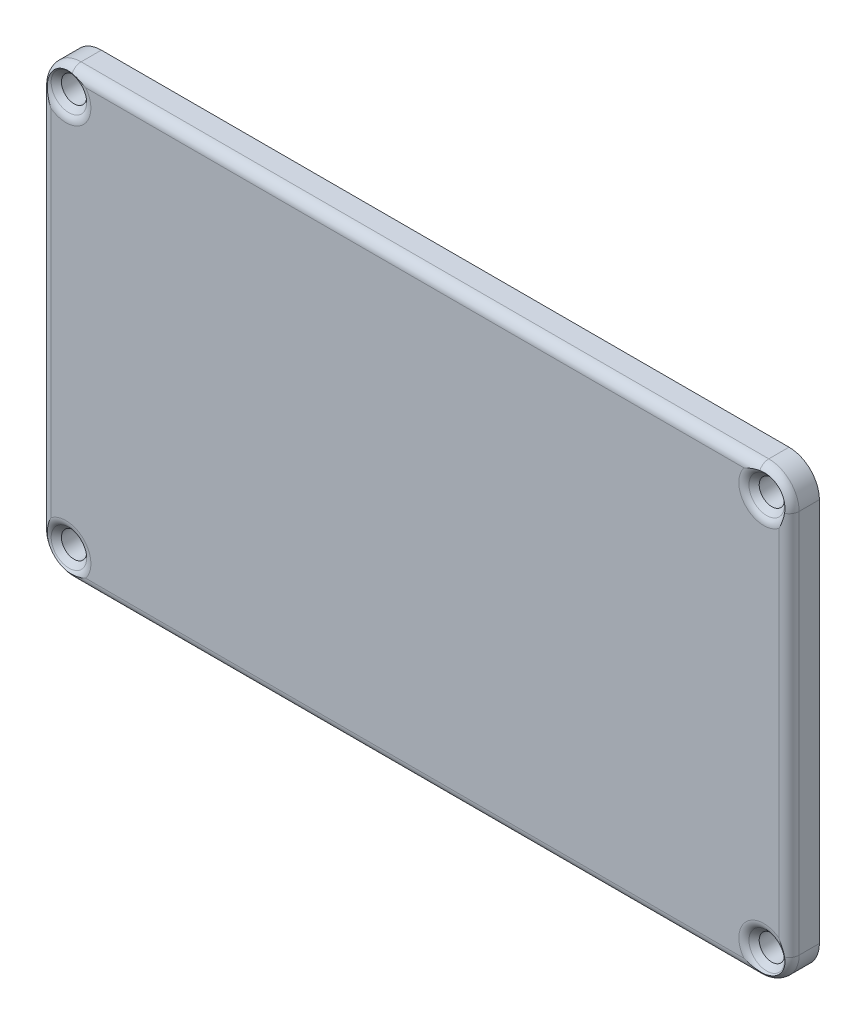
SolidWorks part; units mm, degrees
ref_plane "Front" through (0, 0, 0) normal (0, 0, 1) x (1, 0, 0)
ref_plane "Top" through (0, 0, 0) normal (0, 1, 0) x (1, 0, 0)
ref_plane "Right" through (0, 0, 0) normal (1, 0, 0) x (0, 0, -1)
sketch "Çizim1" plane through (0, 0, 0) normal (0, 0, 1) x (1, 0, 0)
  line L1 (-37, 22) -> (37, 22)
  line L2 (-37, 22) -> (-37, -22)
  line L3 (-37, -22) -> (37, -22)
  line L4 (37, 22) -> (37, -22)
  line L5 (-37, 22) -> (37, -22) construction
  line L6 (-37, -22) -> (37, 22) construction
  point P0 (0, 0)
  dimension "D1" = 74
  dimension "D2" = 44
extrude "Yükseklik-Ekstrüzyon1" add sketch "Çizim1" along normal blind 3
sketch "Çizim2" plane through (0, 0, 3) normal (0, 0, 1) x (1, 0, 0)
  line L1 (-34.5, 19.5) -> (34.5, 19.5) construction
  line L2 (-34.5, 19.5) -> (-34.5, -19.5) construction
  line L3 (-34.5, -19.5) -> (34.5, -19.5) construction
  line L4 (34.5, 19.5) -> (34.5, -19.5) construction
  line L5 (-34.5, 19.5) -> (34.5, -19.5) construction
  line L6 (-34.5, -19.5) -> (34.5, 19.5) construction
  circle A0 centre (-34.5, 19.5) radius 1.25
  circle A1 centre (-34.5, -19.5) radius 1.25
  circle A2 centre (34.5, 19.5) radius 1.25
  circle A3 centre (34.5, -19.5) radius 1.25
  point P0 (0, 0)
  dimension "D1" = 2.5
  dimension "D2" = 69
  dimension "D3" = 39
extrude "Kes-Ekstrüzyon1" cut sketch "Çizim2" against normal through all
fillet "Radyus1" radius 3 4 edges at (-37, -22, 1.5) (37, -22, 1.5) (37, 22, 1.5) (-37, 22, 1.5)
chamfer "Pah1" distance 0.8 angle 45 4 edges at (35.75, 19.5, 3) (35.75, -19.5, 3) (-33.25, -19.5, 3) (-33.25, 19.5, 3)
fillet "Radyus2" radius 1 12 edges at (-36.1213, 21.1213, 3) (0, 22, 3) (36.1213, 21.1213, 3) (37, 0, 3) (36.1213, -21.1213, 3) (0, -22, 3) (-36.1213, -21.1213, 3) (-37, 0, 3) (-32.45, 19.5, 3) (-32.45, -19.5, 3) (36.55, -19.5, 3) (36.55, 19.5, 3)
